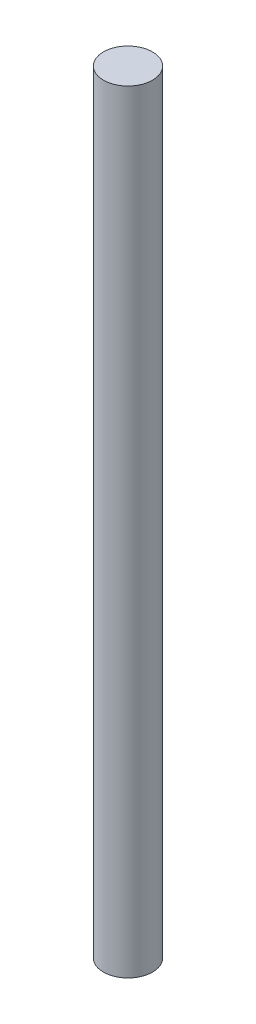
SolidWorks part; units mm, degrees
ref_plane "Front Plane" through (0, 0, 0) normal (0, 0, 1) x (1, 0, 0)
ref_plane "Top Plane" through (0, 0, 0) normal (0, 1, 0) x (1, 0, 0)
ref_plane "Right Plane" through (0, 0, 0) normal (1, 0, 0) x (0, 0, -1)
sketch "Sketch1" plane through (0, 0, 0) normal (0, 1, 0) x (1, 0, 0)
  circle A0 centre (0, 0) radius 3.175
  point P3 (0, 0)
  dimension "D1" = 6.35
extrude "Boss-Extrude1" add sketch "Sketch1" along normal blind 100
